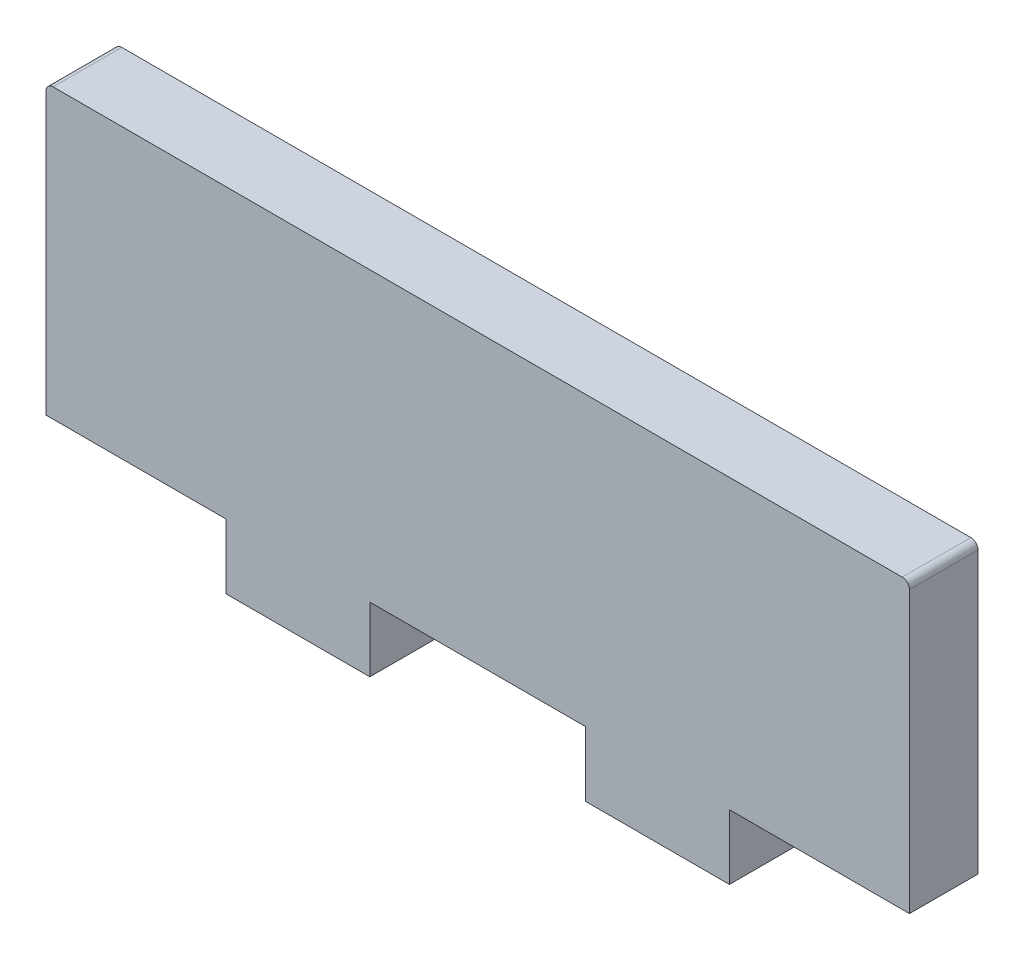
SolidWorks part; units mm, degrees
material "PC High Viscosity"
ref_plane "Front Plane" through (0, 0, 0) normal (0, 0, 1) x (1, 0, 0)
ref_plane "Top Plane" through (0, 0, 0) normal (0, 1, 0) x (1, 0, 0)
ref_plane "Right Plane" through (0, 0, 0) normal (1, 0, 0) x (0, 0, -1)
sketch "Sketch1" plane through (0, 0, 0) normal (0, 0, 1) x (1, 0, 0)
  line L1 (-60, 20) -> (60, 20)
  line L2 (-60, 20) -> (-60, -20)
  line L3 (-60, -20) -> (60, -20)
  line L4 (60, 20) -> (60, -20)
  line L5 (-60, 20) -> (60, -20) construction
  line L6 (-60, -20) -> (60, 20) construction
  line L7 (-34.98, -20) -> (-15, -20)
  line L8 (-34.98, -20) -> (-34.98, -29)
  line L9 (-34.98, -29) -> (-15, -29)
  line L10 (-15, -20) -> (-15, -29)
  line L11 (-34.98, -20) -> (-15, -29) construction
  line L12 (-34.98, -29) -> (-15, -20) construction
  line L13 (15, -20) -> (34.98, -20)
  line L14 (15, -20) -> (15, -29)
  line L15 (15, -29) -> (34.98, -29)
  line L16 (34.98, -20) -> (34.98, -29)
  line L17 (15, -20) -> (34.98, -29) construction
  line L18 (15, -29) -> (34.98, -20) construction
  point P4 (0, 0)
  point P11 (-24.99, -24.5)
  point P15 (24.99, -24.5)
  dimension "D1" = 19.98
  dimension "D2" = 15
  dimension "D3" = 15
  dimension "D4" = 9
  dimension "D5" = 120
  dimension "D6" = 40
extrude "Boss-Extrude1" add sketch "Sketch1" along normal mid plane 9.525 contours L4 L1 L2 L3 | L10 L3 L8 L9 | L16 L3 L14 L15 region at (0, 0, 0) region at (-24.99, -24.5, 0) region at (24.99, -24.5, 0)
fillet "Fillet1" radius 1 2 edges at (60, 20, 0) (-60, 20, 0)
equation "\"D1@Sketch1\"=20-\"tol_general_clear\"*2"
equation "\"tol_dia_id_intfc\" = 0.0200mm ' For hole diameters - Interference fit"
equation "\"tol_dia_id_slip\"  = 0.0300mm ' For hole diameters - Slip fit"
equation "\"tol_dia_id_clear\" = 0.0500mm ' For hole diameters - Clearance fit"
equation "\"tol_dia_od_intfc\" = 0.0200mm ' For shaft diameters - Interference fit"
equation "\"tol_dia_od_slip\"  = 0.0300mm ' For shaft diameters - Slip fit"
equation "\"tol_dia_od_clear\" = 0.0500mm ' For shaft diameters - Clearance fit"
equation "\"tol_general_intfc\"= 0.0030mm ' For general parts (Horiz) - Interference fit"
equation "\"tol_general_slip\" = 0.0050mm ' For general parts (Horiz) - Slip fit"
equation "\"tol_general_clear\"= 0.0100mm ' For general parts (Horiz) - Clearance fit"
equation "\"tol_layer_intfc\"  = 0.0030mm ' For all parts (Vert) - Interference fit"
equation "\"tol_layer_slip\"   = 0.0050mm ' For all parts (Vert) - Slip fit"
equation "\"tol_layer_clear\"  = 0.0100mm ' For all parts (Vert) - Clearance fit"
equation "\"tol_corner_rad\"   = 0.100mm ' For corners that fit into other parts"
equation "\"D3@Sketch1\"=\"D2@Sketch1\""
